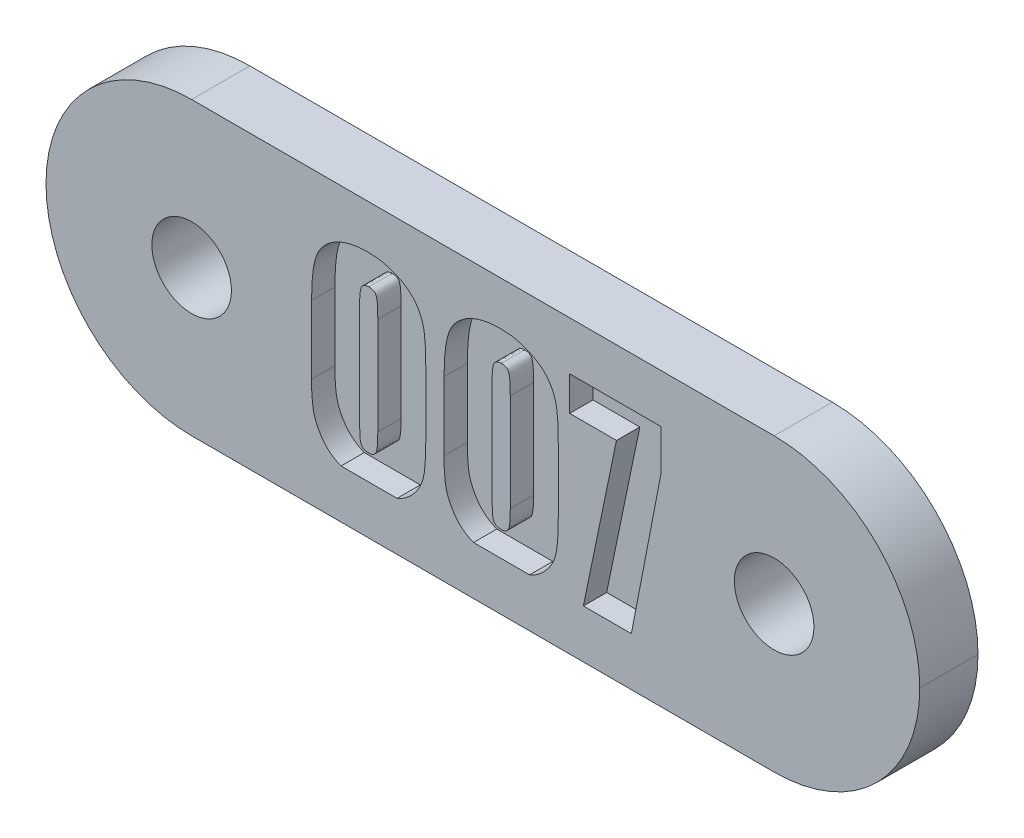
SolidWorks part; units mm, degrees
ref_plane "Front Plane" through (0, 0, 0) normal (0, 0, 1) x (1, 0, 0)
ref_plane "Top Plane" through (0, 0, 0) normal (0, 1, 0) x (1, 0, 0)
ref_plane "Right Plane" through (0, 0, 0) normal (1, 0, 0) x (0, 0, -1)
sketch "Sketch1" plane through (0, 0, 0) normal (0, 0, 1) x (1, 0, 0)
  line L1 (-22.5, 7.5) -> (22.5, 7.5)
  line L2 (-22.5, 7.5) -> (-22.5, -7.5)
  line L3 (-22.5, -7.5) -> (22.5, -7.5)
  line L4 (22.5, 7.5) -> (22.5, -7.5)
  line L5 (-22.5, 7.5) -> (22.5, -7.5) construction
  line L6 (-22.5, -7.5) -> (22.5, 7.5) construction
  point P0 (0, 0)
  dimension "D1" = 45
  dimension "D2" = 15
extrude "Boss-Extrude1" add sketch "Sketch1" along normal blind 3
sketch "Sketch2" plane through (0, 0, 3) normal (0, 0, 1) x (1, 0, 0)
  circle A0 centre (15, 0) radius 2.05
  circle A1 centre (-15, 0) radius 2.05
  dimension "D1" = 4.1
  dimension "D2" = 30
  dimension "D3" = 15
extrude "Cut-Extrude1" cut sketch "Sketch2" against normal blind 4
sketch "Sketch5" plane through (0, 0, 3) normal (0, 0, 1) x (1, 0, 0)
  line L0 (-11, -5) -> (11, -5)
  line L2 (-2.9412, 1.6287) -> (-2.9412, -1.7353)
  line L3 (-8.8235, -1.8897) -> (-8.8235, 1.6287)
  line L4 (-6.3529, 2.4908) -> (-6.3529, -2.4596)
  line L5 (-5.4118, -2.5349) -> (-5.4118, 2.4908)
  line L6 (3.8824, 1.6287) -> (3.8824, -1.7353)
  line L7 (-2, -1.8897) -> (-2, 1.6287)
  line L8 (0.4706, 2.4908) -> (0.4706, -2.4596)
  line L9 (1.4118, -2.5349) -> (1.4118, 2.4908)
  line L10 (9.1765, 5) -> (9.1765, 2.9118)
  line L11 (9.1765, 2.9118) -> (7.6471, -5)
  line L12 (7.6471, -5) -> (5.1765, -5)
  line L13 (5.1765, -5) -> (6.8824, 3.2353)
  line L14 (6.8824, 3.2353) -> (4.4706, 3.2353)
  line L15 (4.4706, 3.2353) -> (4.4706, 5)
  line L16 (4.4706, 5) -> (9.1765, 5)
  spline S0 degree 3 poles (-2.9412, -1.7353) (-2.9408, -1.913) (-2.9449, -2.1704) (-2.9557, -2.5002) (-2.9722, -2.7188) (-2.9863, -2.9177) (-3.0101, -3.097) (-3.0323, -3.2575) (-3.0712, -3.4455) (-3.1387, -3.6644) (-3.2499, -3.9155) (-3.3966, -4.1568) (-3.5737, -4.386) (-3.7748, -4.5972) (-4.0023, -4.7766) (-4.2476, -4.9275) (-4.515, -5.043) (-4.7995, -5.1277) (-5.2075, -5.2144) (-5.5264, -5.2336) (-5.7426, -5.2353) knots 0 0 0 0 0.102604 0.148628 0.190468 0.22916 0.263737 0.294856 0.322678 0.374488 0.426751 0.480869 0.537122 0.593665 0.648803 0.703893 0.759497 0.816458 0.875017 1 1 1 1
  spline S1 degree 3 poles (-5.7426, -5.2353) (-6.0162, -5.2337) (-6.4114, -5.2176) (-6.9066, -5.1245) (-7.2265, -5.0367) (-7.5117, -4.9165) (-7.7642, -4.7655) (-7.99, -4.5892) (-8.1798, -4.3809) (-8.3418, -4.1579) (-8.4785, -3.9256) (-8.5935, -3.6898) (-8.6671, -3.4841) (-8.7147, -3.3088) (-8.7423, -3.1586) (-8.7689, -2.9908) (-8.7878, -2.8054) (-8.8052, -2.602) (-8.8188, -2.2949) (-8.825, -2.0552) (-8.8235, -1.8897) knots 0 0 0 0 0.15504 0.222773 0.284785 0.342425 0.397312 0.450868 0.503863 0.556225 0.606593 0.65622 0.704478 0.729962 0.758931 0.790855 0.826083 0.864351 0.906358 1 1 1 1
  spline S2 degree 3 poles (-8.8235, 1.6287) (-8.8236, 1.8457) (-8.8173, 2.1609) (-8.7927, 2.5659) (-8.7667, 2.8375) (-8.7353, 3.0869) (-8.6918, 3.314) (-8.6454, 3.52) (-8.5898, 3.707) (-8.5237, 3.8797) (-8.4397, 4.0393) (-8.3439, 4.1922) (-8.2313, 4.3346) (-8.106, 4.4701) (-7.9648, 4.5951) (-7.8104, 4.7131) (-7.6413, 4.8213) (-7.4603, 4.9177) (-7.2696, 5.0033) (-7.069, 5.0745) (-6.859, 5.1334) (-6.6397, 5.1791) (-6.3295, 5.2248) (-6.0902, 5.2327) (-5.9283, 5.2353) knots 0 0 0 0 0.121111 0.175939 0.226441 0.27336 0.316156 0.35548 0.391186 0.424974 0.458474 0.491682 0.525548 0.559668 0.594546 0.630663 0.668042 0.706448 0.745028 0.784621 0.825117 0.866705 0.909558 1 1 1 1
  spline S3 degree 3 poles (-5.9283, 5.2353) (-5.6681, 5.2333) (-5.2831, 5.2052) (-4.7954, 5.0791) (-4.4626, 4.9529) (-4.162, 4.8012) (-3.8954, 4.6348) (-3.6711, 4.449) (-3.4877, 4.2451) (-3.3407, 4.0263) (-3.2152, 3.7979) (-3.12, 3.5534) (-3.0622, 3.3381) (-3.0247, 3.1521) (-3.0044, 2.9916) (-2.9837, 2.8122) (-2.9669, 2.613) (-2.9574, 2.3946) (-2.9435, 2.0645) (-2.9415, 1.807) (-2.9412, 1.6287) knots 0 0 0 0 0.143725 0.211434 0.277217 0.33964 0.396925 0.450194 0.499732 0.547635 0.595269 0.643218 0.69192 0.718101 0.747782 0.781111 0.817739 0.858008 0.901639 1 1 1 1
  spline S4 degree 3 poles (-5.4118, 2.4908) (-5.412, 2.6128) (-5.415, 2.7862) (-5.4214, 3.005) (-5.4313, 3.141) (-5.441, 3.2584) (-5.456, 3.3564) (-5.472, 3.4358) (-5.4946, 3.5156) (-5.54, 3.5969) (-5.6679, 3.6882) (-5.7898, 3.7068) (-5.8732, 3.7059) knots 0 0 0 0 0.247595 0.35216 0.444428 0.524395 0.591076 0.645728 0.688625 0.759458 0.829622 1 1 1 1
  spline S5 degree 3 poles (-5.8732, 3.7059) (-5.9555, 3.7069) (-6.0805, 3.6878) (-6.2065, 3.5881) (-6.2557, 3.504) (-6.2843, 3.4216) (-6.3011, 3.3404) (-6.3183, 3.2425) (-6.3299, 3.1263) (-6.3414, 2.9928) (-6.3512, 2.7789) (-6.3518, 2.6097) (-6.3529, 2.4908) knots 0 0 0 0 0.169513 0.24293 0.318863 0.363704 0.419819 0.486676 0.565508 0.6566 0.7587 1 1 1 1
  spline S6 degree 3 poles (-6.3529, -2.4596) (-6.3514, -2.5919) (-6.3518, -2.7796) (-6.3408, -3.0154) (-6.332, -3.1595) (-6.3214, -3.2822) (-6.3081, -3.3825) (-6.2893, -3.461) (-6.2651, -3.5367) (-6.2127, -3.608) (-6.0875, -3.6916) (-5.9673, -3.7071) (-5.886, -3.7059) knots 0 0 0 0 0.261808 0.370991 0.466926 0.547244 0.614602 0.666926 0.706792 0.771036 0.837262 1 1 1 1
  spline S7 degree 3 poles (-5.886, -3.7059) (-5.8035, -3.707) (-5.6798, -3.6878) (-5.5544, -3.5901) (-5.5069, -3.5068) (-5.4792, -3.4263) (-5.4607, -3.3475) (-5.4482, -3.2525) (-5.4313, -3.1414) (-5.4244, -3.0129) (-5.4127, -2.809) (-5.4134, -2.6476) (-5.4118, -2.5349) knots 0 0 0 0 0.174906 0.248855 0.32544 0.371707 0.427109 0.494621 0.572295 0.662349 0.763853 1 1 1 1
  spline S8 degree 3 poles (3.8824, -1.7353) (3.8827, -1.913) (3.8786, -2.1704) (3.8678, -2.5002) (3.8514, -2.7188) (3.8372, -2.9177) (3.8135, -3.097) (3.7913, -3.2575) (3.7523, -3.4455) (3.6849, -3.6644) (3.5737, -3.9155) (3.4269, -4.1568) (3.2499, -4.386) (3.0487, -4.5972) (2.8213, -4.7766) (2.5759, -4.9275) (2.3085, -5.043) (2.024, -5.1277) (1.616, -5.2144) (1.2971, -5.2336) (1.0809, -5.2353) knots 0 0 0 0 0.102604 0.148628 0.190468 0.22916 0.263737 0.294856 0.322678 0.374488 0.426751 0.480869 0.537122 0.593665 0.648803 0.703893 0.759497 0.816458 0.875017 1 1 1 1
  spline S9 degree 3 poles (1.0809, -5.2353) (0.8073, -5.2337) (0.4121, -5.2176) (-0.0831, -5.1245) (-0.403, -5.0367) (-0.6882, -4.9165) (-0.9407, -4.7655) (-1.1665, -4.5892) (-1.3563, -4.3809) (-1.5183, -4.1579) (-1.655, -3.9256) (-1.77, -3.6898) (-1.8435, -3.4841) (-1.8912, -3.3088) (-1.9188, -3.1586) (-1.9454, -2.9908) (-1.9642, -2.8054) (-1.9817, -2.602) (-1.9953, -2.2949) (-2.0015, -2.0552) (-2, -1.8897) knots 0 0 0 0 0.15504 0.222773 0.284785 0.342425 0.397312 0.450868 0.503863 0.556225 0.606593 0.65622 0.704478 0.729962 0.758931 0.790855 0.826083 0.864351 0.906358 1 1 1 1
  spline S10 degree 3 poles (-2, 1.6287) (-2.0001, 1.8457) (-1.9937, 2.1609) (-1.9692, 2.5659) (-1.9432, 2.8375) (-1.9118, 3.0869) (-1.8682, 3.314) (-1.8219, 3.52) (-1.7662, 3.707) (-1.7002, 3.8797) (-1.6162, 4.0393) (-1.5204, 4.1922) (-1.4077, 4.3346) (-1.2824, 4.4701) (-1.1413, 4.5951) (-0.9869, 4.7131) (-0.8178, 4.8213) (-0.6368, 4.9177) (-0.4461, 5.0033) (-0.2455, 5.0745) (-0.0355, 5.1334) (0.1838, 5.1791) (0.494, 5.2248) (0.7334, 5.2327) (0.8952, 5.2353) knots 0 0 0 0 0.121111 0.175939 0.226441 0.27336 0.316156 0.35548 0.391186 0.424974 0.458474 0.491682 0.525548 0.559668 0.594546 0.630663 0.668042 0.706448 0.745028 0.784621 0.825117 0.866705 0.909558 1 1 1 1
  spline S11 degree 3 poles (0.8952, 5.2353) (1.1554, 5.2333) (1.5404, 5.2052) (2.0281, 5.0791) (2.3609, 4.9529) (2.6616, 4.8012) (2.9281, 4.6348) (3.1524, 4.449) (3.3359, 4.2451) (3.4828, 4.0263) (3.6083, 3.7979) (3.7035, 3.5534) (3.7613, 3.3381) (3.7988, 3.1521) (3.8191, 2.9916) (3.8398, 2.8122) (3.8566, 2.613) (3.8661, 2.3946) (3.88, 2.0645) (3.882, 1.807) (3.8824, 1.6287) knots 0 0 0 0 0.143725 0.211434 0.277217 0.33964 0.396925 0.450194 0.499732 0.547635 0.595269 0.643218 0.69192 0.718101 0.747782 0.781111 0.817739 0.858008 0.901639 1 1 1 1
  spline S12 degree 3 poles (1.4118, 2.4908) (1.4115, 2.6128) (1.4085, 2.7862) (1.4021, 3.005) (1.3922, 3.141) (1.3825, 3.2584) (1.3676, 3.3564) (1.3515, 3.4358) (1.329, 3.5156) (1.2836, 3.5969) (1.1556, 3.6882) (1.0337, 3.7068) (0.9504, 3.7059) knots 0 0 0 0 0.247595 0.35216 0.444428 0.524395 0.591076 0.645728 0.688625 0.759458 0.829622 1 1 1 1
  spline S13 degree 3 poles (0.9504, 3.7059) (0.868, 3.7069) (0.743, 3.6878) (0.6171, 3.5881) (0.5678, 3.504) (0.5392, 3.4216) (0.5225, 3.3404) (0.5052, 3.2425) (0.4936, 3.1263) (0.4821, 2.9928) (0.4723, 2.7789) (0.4718, 2.6097) (0.4706, 2.4908) knots 0 0 0 0 0.169513 0.24293 0.318863 0.363704 0.419819 0.486676 0.565508 0.6566 0.7587 1 1 1 1
  spline S14 degree 3 poles (0.4706, -2.4596) (0.4721, -2.5919) (0.4717, -2.7796) (0.4827, -3.0154) (0.4915, -3.1595) (0.5021, -3.2822) (0.5155, -3.3825) (0.5342, -3.461) (0.5584, -3.5367) (0.6108, -3.608) (0.7361, -3.6916) (0.8562, -3.7071) (0.9375, -3.7059) knots 0 0 0 0 0.261808 0.370991 0.466926 0.547244 0.614602 0.666926 0.706792 0.771036 0.837262 1 1 1 1
  spline S15 degree 3 poles (0.9375, -3.7059) (1.02, -3.707) (1.1437, -3.6878) (1.2691, -3.5901) (1.3167, -3.5068) (1.3443, -3.4263) (1.3628, -3.3475) (1.3753, -3.2525) (1.3923, -3.1414) (1.3991, -3.0129) (1.4109, -2.809) (1.4101, -2.6476) (1.4118, -2.5349) knots 0 0 0 0 0.174906 0.248855 0.32544 0.371707 0.427109 0.494621 0.572295 0.662349 0.763853 1 1 1 1
  point P1 (0, -5)
  dimension "D1" = 5
extrude "Cut-Extrude2" cut sketch "Sketch5" against normal blind 1.2 contours S3 S2 L3 S1 L0 S0 L2 S7 S6 L4 S5 S4 L5 | S11 S10 L7 S9 L0 S8 L6 S15 S14 L8 S13 S12 L9 | L16 L15 L14 L13 L0 L11 L10 region at (7.1093, 0.5673, 3) region at (-5.8633, -4.8819, 3) region at (0.9602, -4.8819, 3)
fillet "Fillet1" radius 7.5 4 edges at (22.5, 7.5, 1.5) (22.5, -7.5, 1.5) (-22.5, -7.5, 1.5) (-22.5, 7.5, 1.5)
